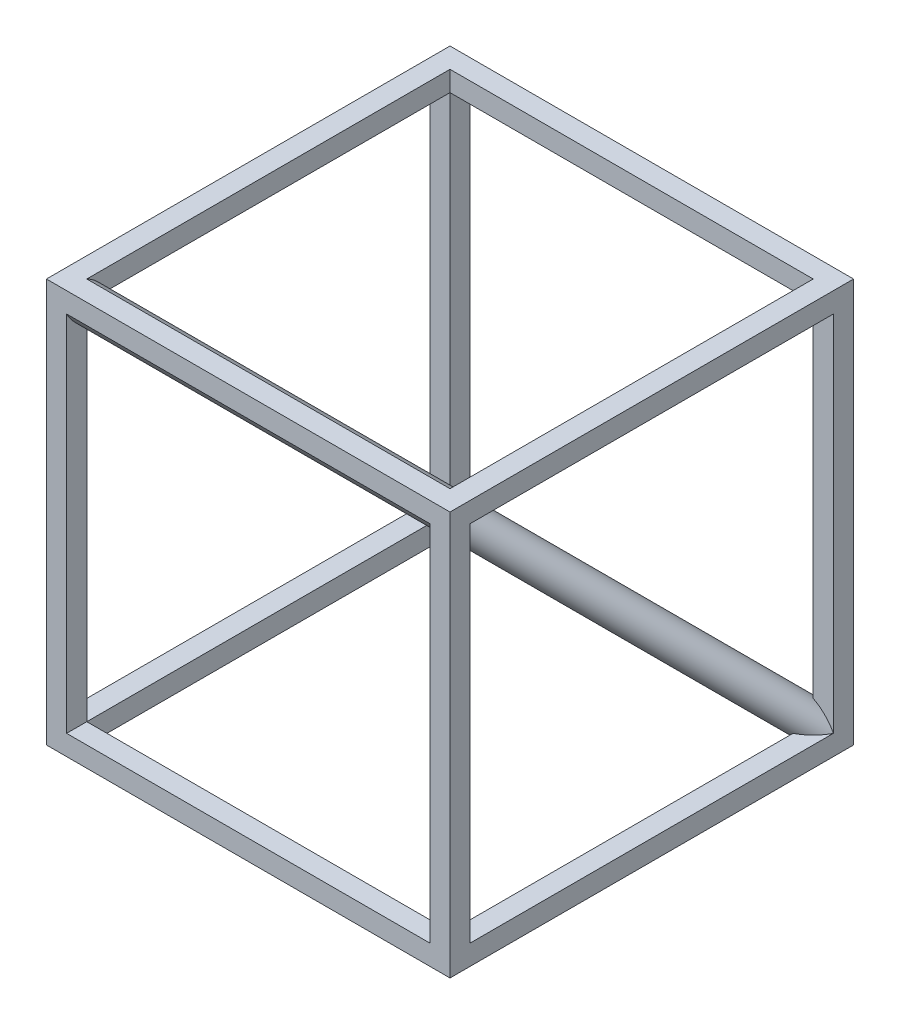
SolidWorks part; units mm, degrees
ref_plane "Front Plane" through (0, 0, 0) normal (0, 0, 1) x (1, 0, 0)
ref_plane "Top Plane" through (0, 0, 0) normal (0, 1, 0) x (1, 0, 0)
ref_plane "Right Plane" through (0, 0, 0) normal (1, 0, 0) x (0, 0, -1)
sketch "Sketch1" plane through (0, 0, 0) normal (0, 1, 0) x (1, 0, 0)
  line L1 (-5, -5) -> (5, -5)
  line L2 (-5, -5) -> (-5, 5)
  line L3 (-5, 5) -> (5, 5)
  line L4 (5, -5) -> (5, 5)
  line L5 (-5, -5) -> (5, 5) construction
  line L6 (-5, 5) -> (5, -5) construction
  point P0 (0, 0)
  dimension "D1" = 10
extrude "Boss-Extrude1" add sketch "Sketch1" along normal blind 10
shell "Shell2" thickness 0.5
sketch3d "3DSketch1"
  line L0 (5, 9.5, 4.5) -> (5, 9.5, -4.5)
  line L1 (5, 9.5, 4.5) -> (5, 0.5, 4.5)
  line L2 (5, 0.5, 4.5) -> (5, 0.5, -4.5)
  line L3 (5, 9.5, -4.5) -> (5, 0.5, -4.5)
  line L4 (5, 9.5, 4.5) -> (5, 9.5, -4.5)
  line L5 (5, 9.5, 4.5) -> (5, 0.5, 4.5)
  line L6 (5, 0.5, 4.5) -> (5, 0.5, -4.5)
  line L7 (5, 9.5, -4.5) -> (5, 0.5, -4.5)
  dimension "D1" = 0.5
extrude "Cut-Extrude1" cut sketch "3DSketch1" along direction (1, 0, 0) on the side against the normal through all
sketch3d "3DSketch2"
  line L0 (-4.5, 9.5, 5) -> (-4.5, 0.5, 5)
  line L1 (-4.5, 0.5, 5) -> (4.5, 0.5, 5)
  line L2 (4.5, 9.5, 5) -> (4.5, 0.5, 5)
  line L3 (-4.5, 9.5, 5) -> (4.5, 9.5, 5)
  line L4 (-4.5, 9.5, 5) -> (-4.5, 0.5, 5)
  line L5 (-4.5, 0.5, 5) -> (4.5, 0.5, 5)
  line L6 (4.5, 9.5, 5) -> (4.5, 0.5, 5)
  line L7 (-4.5, 9.5, 5) -> (4.5, 9.5, 5)
  dimension "D1" = 0.5
extrude "Cut-Extrude2" cut sketch "3DSketch2" along direction (0, 0, 1) on the side of the normal through all
ref_plane "Plane1" through (-6.3333, 6.3333, 6.3333) normal (-0.5774, 0.5774, 0.5774) x (0.8165, 0.4082, 0.4082)
sketch "Sketch5" plane through (-6.3333, 6.3333, 6.3333) normal (-0.5774, 0.5774, 0.5774) x (0.8165, 0.4082, 0.4082)
  circle A0 centre (2.0412, 3.5355) radius 0.4082
extrude "Boss-Extrude6" add sketch "Sketch5" against normal blind 16.15
ref_plane "Plane2" through (-3, -3, -3) normal (0.5774, 0.5774, 0.5774) x (0.8165, -0.4082, -0.4082)
sketch "Sketch9" plane through (-3, -3, -3) normal (0.5774, 0.5774, 0.5774) x (0.8165, -0.4082, -0.4082)
  circle A0 centre (-2.0412, 3.5355) radius 0.4082
extrude "Boss-Extrude5" add sketch "Sketch9" along normal blind 16.15
ref_plane "Plane3" through (3, -3, 3) normal (-0.5774, 0.5774, -0.5774) x (-0.8165, -0.4082, 0.4082)
